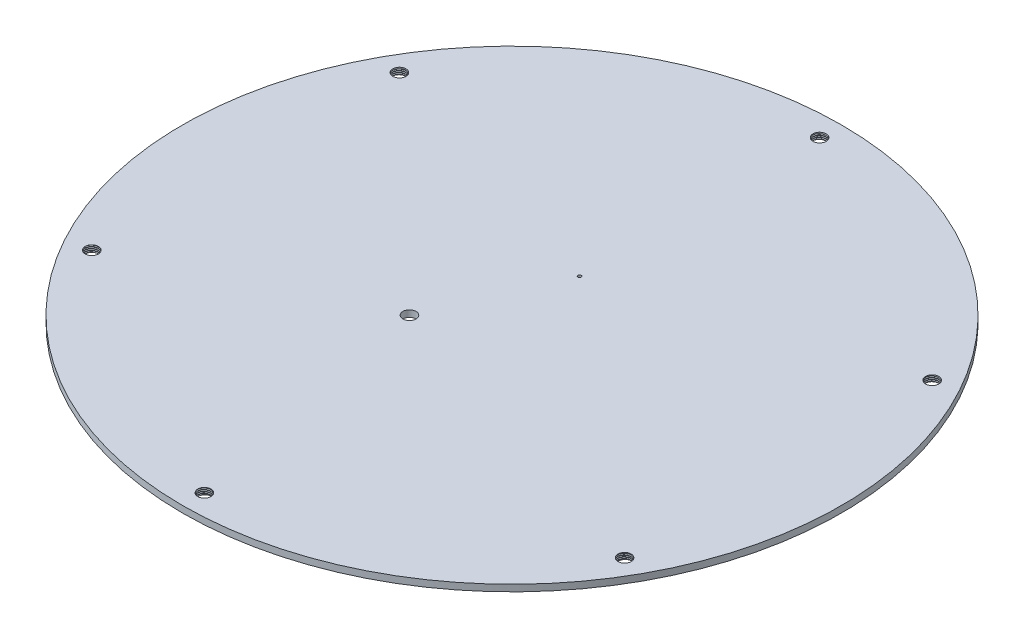
SolidWorks part; units mm, degrees
material "1060 Alloy"
ref_plane "Front Plane" through (0, 0, 0) normal (0, 0, 1) x (1, 0, 0)
ref_plane "Top Plane" through (0, 0, 0) normal (0, 1, 0) x (1, 0, 0)
ref_plane "Right Plane" through (0, 0, 0) normal (1, 0, 0) x (0, 0, -1)
sketch "Sketch1" plane through (0, 0, 0) normal (0, 1, 0) x (1, 0, 0)
  circle A0 centre (0, 0) radius 50
  circle A1 centre (0, 46.67) radius 1
  circle A2 centre (40.4174, 23.335) radius 1
  circle A3 centre (40.4174, -23.335) radius 1
  circle A4 centre (0, -46.67) radius 1
  circle A5 centre (-40.4174, -23.335) radius 1
  circle A6 centre (-40.4174, 23.335) radius 1
  point P17 (0, 0)
  dimension "D1" = 100
  dimension "D2" = 2
  dimension "D3" = 46.67
  dimension "D4" = 6
extrude "Boss-Extrude1" add sketch "Sketch1" along normal blind 1
thread "Thread1" pitch 0.25 method cut profile "Thread Profile1" start angle 0, offset 0, length 10, pitch 0.25, diameter 2
ref_plane "Plane1" through (-41.4174, 1, 23.335) normal (0, 0, 1) x (-1, 0, 0)
sketch "Thread Profile1" plane through (-41.4174, 1, 23.335) normal (0, 0, 1) x (-1, 0, 0)
  line L0 (0, 0) -> (0, 0.25) construction
  line L1 (0, 0) -> (0.1353, 0.0781)
  line L2 (0.1353, 0.0781) -> (0.1353, 0.1094)
  line L3 (0.1353, 0.1094) -> (0, 0.1875)
  line L4 (0.1353, 0.0937) -> (0, 0.0937) construction
  line L11 (0, 0) -> (0, 0.1875)
  point P2 (0, 0)
  dimension "Pitch" = 0.25
  dimension "Profile_Angle" = 60
  dimension "Profile_Land" = 0.0312
  dimension "Profile_Height" = 0.1353
pattern_circular "CirPattern1" count 6 over 360 about axis through (0, 0, 0) along (0, 1, 0) of "Thread1"
sketch "Sketch2" plane through (0, 1, 0) normal (0, 1, 0) x (1, 0, 0)
  line L0 (0, 0) -> (0, 10.25) construction
  line L1 (0, 10.25) -> (0, 0) construction
  line L2 (0, 0) -> (-20.5223, -20.5223) construction
  circle A0 centre (0, 10.25) radius 0.25
  circle A1 centre (-7.7782, -7.7782) radius 1
  dimension "D1" = 0.5
  dimension "D3" = 2
  dimension "D2" = 10.25
  dimension "D4" = 11
extrude "Cut-Extrude1" cut sketch "Sketch2" against normal through all both and the other way through all
